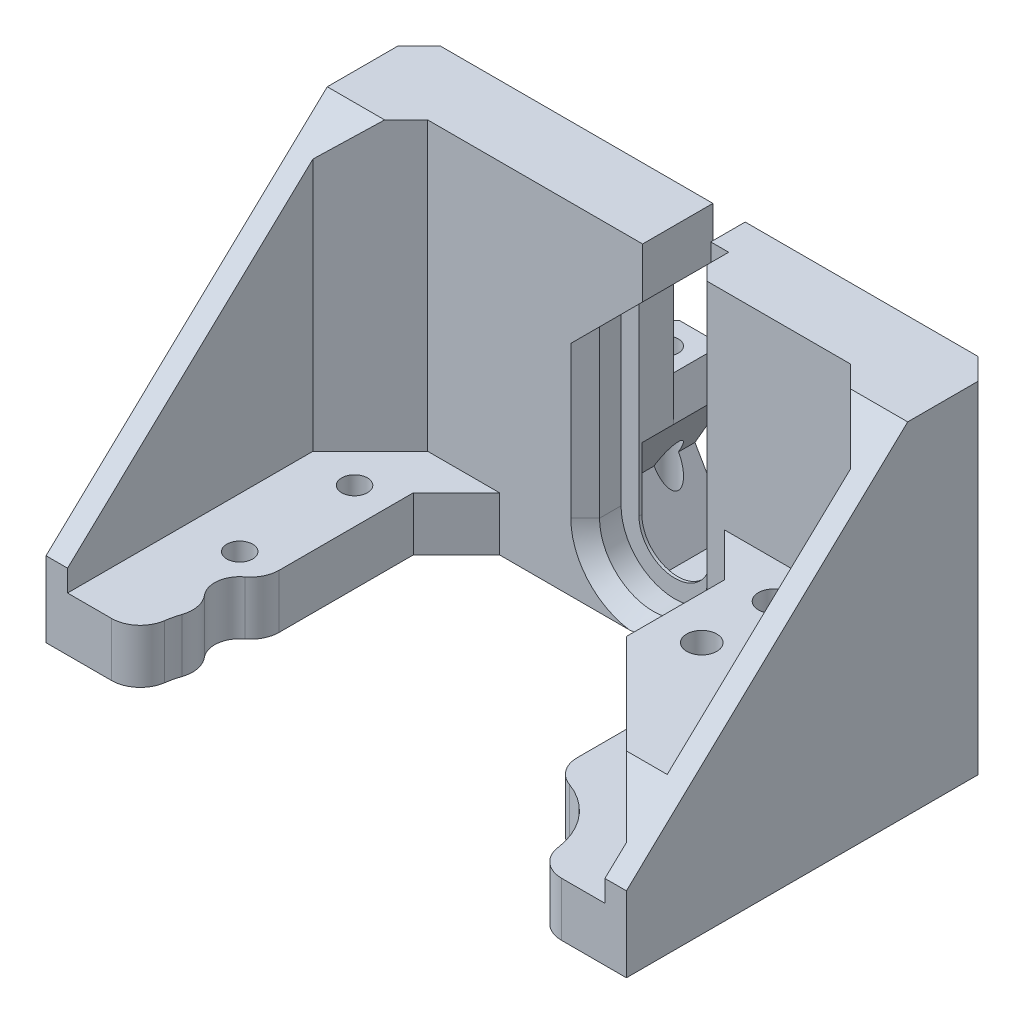
SolidWorks part; units mm, degrees
ref_plane "Front Plane" through (0, 0, 0) normal (0, 0, 1) x (1, 0, 0)
ref_plane "Top Plane" through (0, 0, 0) normal (0, 1, 0) x (1, 0, 0)
ref_plane "Right Plane" through (0, 0, 0) normal (1, 0, 0) x (0, 0, -1)
sketch "Sketch1" plane through (0, 0, 0) normal (0, 1, 0) x (1, 0, 0)
  line L0 (0, 0) -> (0, -16) construction
  line L1 (54.39, 4) -> (54.39, -6) construction
  line L2 (48.39, 9.2) -> (48.39, -33)
  line L3 (48.39, -33) -> (67.89, -33)
  line L4 (67.89, -33) -> (67.89, 19)
  line L5 (67.89, 19) -> (-7, 19)
  line L6 (-7, 19) -> (-7, -33)
  line L7 (-7, -33) -> (5, -33)
  line L8 (5, -33) -> (5, 9.2)
  line L9 (5, 9.2) -> (48.39, 9.2)
  circle A0 centre (0, 0) radius 1
  circle A1 centre (0, -16) radius 1
  circle A2 centre (54.39, 4) radius 1
  circle A3 centre (54.39, -6) radius 1
  dimension "D1" = 16
  dimension "D2" = 10
  dimension "D3" = 10
  dimension "D5" = 17
  dimension "D7" = 2
  dimension "D10" = 9.2
  dimension "D4" = 52
  dimension "D6" = 5
  dimension "D8" = 6
  dimension "D9" = 54.39
  dimension "D11" = 12
  dimension "D12" = 19.5
extrude "Boss-Extrude1" add sketch "Sketch1" along normal blind 7.5
hole_wizard "CSK for M3 Hex Socket Countersunk Head Screw1" positions "Sketch2" profile "Sketch3" countersink size "M3" standard "DIN" end condition through all
sketch "Sketch2" plane through (0, 0, 0) normal (0, -1, 0) x (-1, 0, 0)
  point P0 (0, 0)
  point P3 (0, -16)
  point P6 (-54.39, 4)
  point P9 (-54.39, -6)
sketch "Sketch3" plane through (0, 0, 0) normal (1, 0, 0) x (0, 0, -1)
  line L0 (0, 0) -> (0, 7.5)
  line L1 (0, 7.5) -> (1.8, 7.5)
  line L2 (1.8, 7.5) -> (1.8, 1.67)
  line L3 (1.8, 1.67) -> (3.47, 0)
  line L5 (3.47, 0) -> (0, 0)
  line L6 (-1.8, 1.67) -> (-3.47, 0) construction
  line L11 (0, -6.35) -> (0, 107.95) construction
  dimension "Thru Hole Dia." = 3.6
  dimension "Thru Hole Depth" = 7.5
  dimension "Near C'Sink Dia." = 6.94
  dimension "Near C'Sink Angle" = 90
sketch "Sketch4" plane through (0, 7.5, 0) normal (0, 1, 0) x (1, 0, 0)
  line L0 (67.89, -33) -> (67.89, 19) construction
  line L1 (-7, 19) -> (67.89, 19)
  line L2 (-7, 19) -> (-7, 9.2)
  line L3 (-7, 9.2) -> (67.89, 9.2)
  line L4 (67.89, 19) -> (67.89, 9.2)
  line L5 (5, 9.2) -> (48.39, 9.2) construction
extrude "Boss-Extrude2" add sketch "Sketch4" along normal blind 40
sketch "Sketch5" plane through (-7, 0, 0) normal (-1, 0, 0) x (0, 0, 1)
  line L0 (-19, 47.5) -> (-6.2, 47.5)
  line L1 (-6.2, 47.5) -> (33, 10.5)
  line L2 (33, 10.5) -> (33, 0)
  line L3 (33, 0) -> (-19, 0)
  line L4 (-19, 0) -> (-19, 47.5)
  line L5 (-9.2, 47.5) -> (-9.2, 7.5) construction
  line L6 (-9.2, 7.5) -> (33, 7.5) construction
  dimension "D1" = 3
  dimension "D2" = 3
extrude "Boss-Extrude3" add sketch "Sketch5" along normal blind 3
extrude "Boss-Extrude4" add sketch "Sketch5<2>" against normal blind 3 from surface starting at face at (67.89, 18.3333, 1.6)
sketch "Sketch5<2>" plane through (-7, 0, 0) normal (-1, 0, 0) x (0, 0, 1) same geometry as "Sketch5"
sketch "Sketch6" plane through (0, 0, 0) normal (0, -1, 0) x (1, 0, 0)
  line L0 (3, 31) -> (3, 33)
  line L1 (-10, 33) -> (5, 33) construction
  line L2 (3, 33) -> (5, 33)
  line L3 (5, 33) -> (5, 24.8356)
  line L4 (5, 33) -> (5, -9.2) construction
  circle A0 centre (13.5, 31) radius 9.5 construction
  circle A1 centre (13.5, 31) radius 9.5 construction
  arc A2 (3, 31) -> (5, 24.8356) centre (13.5, 31) ccw
  circle A3 centre (13.5, 31) radius 10.5 construction
  circle A4 centre (5.5, 21.5) radius 1.5 construction
  circle A5 centre (5.5, 21.5) radius 1.5 construction
  circle A6 centre (5.5, 21.5) radius 3.5
  circle A7 centre (47.5, 31) radius 9.5 construction
  circle A8 centre (47.5, 31) radius 9.5 construction
  circle A9 centre (47.5, 31) radius 10.5
  line M7 (5, -9.2) -> (5, 33)
  line M8 (5, 33) -> (-10, 33)
  dimension "D2" = 2
  dimension "D1" = 1
  dimension "D3" = 1
extrude "Cut-Extrude1" cut sketch "Sketch6" against normal through all contours A6 L3 L0 A2 M8 | A6 A2 M7 | A2 A6 M7 | A9 region at (4.1304, 0, 29.7376) region at (4.9724, 0, 24.917) region at (3.7405, 0, 21.4988)
fillet "Fillet1" radius 4 5 edges at (3, 3.75, 33) (4.9174, 3.75, 24.9512) (5, 3.75, 18.0359) (57.8078, 3.75, 33) (48.39, 3.75, 20.5378)
sketch "Sketch7" plane through (0, 7.5, 0) normal (0, 1, 0) x (1, 0, 0)
  line L0 (67.89, -33) -> (67.89, 9.2) construction
  line L1 (48.39, 9.2) -> (67.89, 9.2)
  line L2 (48.39, 9.2) -> (48.39, -10)
  line L3 (48.39, -10) -> (67.89, -10)
  line L4 (67.89, 9.2) -> (67.89, -10)
  circle A0 centre (54.39, -6) radius 4 construction
  dimension "D1" = 8
extrude "Boss-Extrude5" add sketch "Sketch7" along normal blind 6 from offset 5.2
hole_wizard "Ø4.2 (4.2) Diameter Hole1" positions "Sketch8" profile "Sketch10" hole size "Ø4.2" standard "DIN" end condition through all
sketch "Sketch8" plane through (0, 12.7, 0) normal (0, -1, 0) x (-1, 0, 0)
  point P0 (-54.39, -6)
  point P3 (-54.39, 4)
sketch "Sketch10" plane through (54.39, 12.7, 6) normal (1, 0, 0) x (0, 0, -1)
  line L0 (0, 0) -> (0, 34.8)
  line L1 (0, 34.8) -> (2.1, 34.8)
  line L2 (2.1, 34.8) -> (2.1, 0)
  line L5 (2.1, 0) -> (0, 0)
  line L11 (0, -6.35) -> (0, 107.95) construction
  dimension "Thru Hole Dia." = 4.2
  dimension "Thru Hole Depth" = 34.8
chamfer "Chamfer1" distance 20 angle 45 1 edges at (67.89, 15.7, 10)
chamfer "Chamfer2" distance 8 angle 45 2 edges at (-7, 27.5, -9.2) (67.89, 33.1, -9.2)
chamfer "Chamfer3" distance 3 angle 45 2 edges at (70.89, 23.75, -19) (-10, 23.75, -19)
chamfer "Chamfer4" distance 6 angle 45 3 edges at (48.39, 15.7, -9.2) (48.39, 3.75, -9.2) (5, 3.75, -9.2)
sketch "Sketch11" plane through (0, 0, -19) normal (0, 0, -1) x (-1, 0, 0)
  line L0 (-70.89, 0) -> (-70.89, 47.5) construction
  line L1 (10, 47.5) -> (10, 0) construction
  line L2 (-70.89, 0) -> (-70.89, 47.5) construction
  line L3 (10, 47.5) -> (10, 0) construction
  line L4 (-70.89, 9.4) -> (-30.445, 9.4) construction
  line L5 (-30.445, 9.4) -> (10, 9.4) construction
  line L6 (-67.89, 0) -> (7, 0) construction
  line L7 (-35.445, 9.4) -> (-35.445, 47.5)
  line L8 (-67.89, 47.5) -> (7, 47.5) construction
  line L9 (-35.445, 47.5) -> (-25.445, 47.5)
  line L10 (-25.445, 47.5) -> (-25.445, 9.4)
  arc A0 (-35.445, 9.4) -> (-25.445, 9.4) centre (-30.445, 9.4) ccw
  dimension "D1" = 9.4
  dimension "D2" = 10
extrude "Cut-Extrude2" cut sketch "Sketch11" against normal through all
sketch "Sketch13" plane through (0, 0, -19) normal (0, 0, -1) x (-1, 0, 0)
  line L0 (-25.445, 9.4) -> (-25.445, 47.5) construction
  line L1 (-35.445, 47.5) -> (-35.445, 9.4) construction
  line L2 (-25.445, 9.4) -> (-25.445, 17.3599)
  line L3 (-35.445, 17.3599) -> (-35.445, 9.4)
  arc A0 (-35.445, 17.3599) -> (-25.445, 17.3599) centre (-30.445, 9.4) ccw
  arc A1 (-35.445, 9.4) -> (-25.445, 9.4) centre (-30.445, 9.4) ccw construction
  arc A2 (-35.445, 9.4) -> (-25.445, 9.4) centre (-30.445, 9.4) ccw
extrude "Boss-Extrude7" [suppressed] add sketch "Sketch13" along normal blind 10
sketch "Sketch14" plane through (0, 0, -9.2) normal (0, 0, 1) x (1, 0, 0)
  line L0 (22.945, 9.4) -> (22.945, 47.5)
  line L1 (1, 47.5) -> (25.445, 47.5) construction
  line L2 (22.945, 47.5) -> (37.945, 47.5)
  line L3 (35.445, 47.5) -> (59.89, 47.5) construction
  line L4 (37.945, 47.5) -> (37.945, 9.4)
  arc A0 (22.945, 9.4) -> (37.945, 9.4) centre (30.445, 9.4) ccw
  dimension "D1" = 15
extrude "Cut-Extrude3" cut sketch "Sketch14" against normal blind 5
sketch "Sketch12" plane through (0, 0, -9.2) normal (0, 0, -1) x (-1, 0, 0)
  line L0 (-22.945, 47.5) -> (-30.945, 47.5)
  line L1 (-30.945, 47.5) -> (-30.945, 40.5)
  line L2 (-30.945, 40.5) -> (-22.945, 32.5)
  line L4 (-22.945, 32.5) -> (-22.945, 47.5)
  line L5 (-35.445, 47.5) -> (-35.445, 9.4) construction
  line L7 (-22.945, 47.5) -> (-22.945, 9.4) construction
  line L8 (-1, 47.5) -> (-22.945, 47.5) construction
  dimension "D1" = 45
  dimension "D2" = 4.5
  dimension "D3" = 15
extrude "Boss-Extrude6" add sketch "Sketch12" along normal up to surface (9.8 mm away) up to face at (30.445, 25.475, -19)
chamfer "Chamfer5" [suppressed] distance 3 angle 45
sketch "Sketch15" plane through (0, 0, -19) normal (0, 0, -1) x (-1, 0, 0)
  line L0 (-21.121, -2.35) -> (-39.769, -2.35)
  line L1 (-35.445, 18.0603) -> (-40.445, 9.4)
  line L2 (-40.445, 9.4) -> (-35.445, 0.7397)
  line L3 (-35.445, 0.7397) -> (-25.445, 0.7397)
  line L4 (-25.445, 0.7397) -> (-20.445, 9.4)
  line L5 (-20.445, 9.4) -> (-25.445, 18.0603)
  line L6 (-25.445, 18.0603) -> (-35.445, 18.0603)
  line L7 (-36.695, 23.0359) -> (-35.445, 18.0603)
  line L8 (-25.445, 18.0603) -> (-24.195, 23.0359)
  circle A0 centre (-30.445, 9.4) radius 10 construction
  circle A1 centre (-30.445, 9.4) radius 8.6603 construction
  arc A2 (-21.121, -2.35) -> (-39.769, -2.35) centre (-30.445, 9.4) ccw
  line M13 (-25.445, 35) -> (-25.445, 9.4)
  line M15 (-35.445, 9.4) -> (-35.445, 47.5)
  line M18 (-67.89, 0) -> (7, 0)
  dimension "D1" = 20
  dimension "D2" = 30
extrude "Boss-Extrude8" add sketch "Sketch15" along normal blind 8 contours A2 L5 L4 L3 L2 L1 M15 M18 M13 region at (30.445, 0.3782, -19)
sketch "Sketch16" plane through (0, 0, -19) normal (0, 0, -1) x (-1, 0, 0)
  line L7 (-25.445, 0.7397) -> (-20.445, 9.4)
  line L8 (-20.445, 9.4) -> (-25.445, 18.0603)
  line L9 (-25.445, 18.0603) -> (-25.445, 9.4)
  line L10 (-35.445, 9.4) -> (-35.445, 18.0603)
  line L11 (-35.445, 18.0603) -> (-40.445, 9.4)
  line L12 (-40.445, 9.4) -> (-35.445, 0.7397)
  line L13 (-35.445, 0.7397) -> (-25.445, 0.7397)
  line L14 (-25.445, 0.7397) -> (-20.445, 9.4)
  line L15 (-20.445, 9.4) -> (-25.445, 18.0603)
  line L16 (-25.445, 18.0603) -> (-25.445, 9.4)
  line L17 (-35.445, 9.4) -> (-35.445, 18.0603)
  line L18 (-35.445, 18.0603) -> (-40.445, 9.4)
  line L19 (-40.445, 9.4) -> (-35.445, 0.7397)
  line L20 (-35.445, 0.7397) -> (-25.445, 0.7397)
  arc A1 (-35.445, 9.4) -> (-25.445, 9.4) centre (-30.445, 9.4) ccw
  arc A2 (-35.445, 9.4) -> (-25.445, 9.4) centre (-30.445, 9.4) ccw
  dimension "D1" = 0
extrude "Cut-Extrude4" cut sketch "Sketch16" against normal blind 4.4
chamfer "Chamfer6" [suppressed] distance 2 angle 45
sketch "Sketch18" plane through (0, 0, -19) normal (0, 0, -1) x (-1, 0, 0)
  line L0 (-67.89, 0) -> (-42.1343, 0) construction
  line L1 (-45.445, 0) -> (-42.1343, 0)
  line L2 (-45.445, 0) -> (-45.445, 23.0359)
  line L3 (-45.445, 23.0359) -> (-36.695, 23.0359)
  line L4 (-15.445, 0) -> (-15.445, 23.0359)
  line L5 (-24.195, 23.0359) -> (-15.445, 23.0359)
  line L6 (-18.7557, 0) -> (-15.445, 0)
  arc A0 (-18.7557, 0) -> (-24.195, 23.0359) centre (-30.445, 9.4) ccw construction
  arc A1 (-36.695, 23.0359) -> (-42.1343, 0) centre (-30.445, 9.4) ccw construction
  arc A2 (-18.7557, 0) -> (-24.195, 23.0359) centre (-30.445, 9.4) ccw construction
  arc A3 (-18.7557, 0) -> (-24.195, 23.0359) centre (-30.445, 9.4) ccw
  arc A4 (-36.695, 23.0359) -> (-42.1343, 0) centre (-30.445, 9.4) ccw
  arc M5 (-24.195, 23.0359) -> (-18.7557, 0) centre (-30.445, 9.4) cw
  line M6 (-18.7557, 0) -> (7, 0)
extrude "Boss-Extrude9" add sketch "Sketch18" along normal up to surface (8 mm away) contours A4 L2 L1 | L4 M6 M5 | L5 L4 M5 | A4 L3 L2 region at (44.4739, 2.295, -19) region at (43.036, 19.8558, -19) region at (16.4161, 2.295, -19) region at (17.854, 19.8558, -19) up to face at (30.445, 10.513, -27)
sketch "Sketch17" plane through (0, 0, 0) normal (0, -1, 0) x (1, 0, 0)
  line L0 (20.445, -27) -> (20.445, -14.6) construction
  line L1 (20.445, -27) -> (20.445, -14.6) construction
  line L2 (30.445, -27) -> (30.445, -19) construction
  line L3 (45.445, -27) -> (15.445, -27) construction
  line L4 (67.89, -19) -> (45.445, -19) construction
  line L5 (30.445, -23) -> (20.445, -23) construction
  circle A0 centre (20.445, -23) radius 1
  circle A1 centre (40.445, -23) radius 1
  point P11 (30.445, -27)
  dimension "D1" = 2
extrude "Cut-Extrude5" cut sketch "Sketch17" against normal through all
hole_wizard "M3 Clearance Hole1" positions "Sketch19" profile "Sketch20" hole size "M3" standard "DIN" end condition through all
sketch "Sketch19" plane through (0, 0, 0) normal (0, -1, 0) x (-1, 0, 0)
  point P0 (-20.445, 23)
  point P3 (-40.445, 23)
sketch "Sketch20" plane through (20.445, 0, -23) normal (1, 0, 0) x (0, 0, -1)
  line L0 (0, 0) -> (0, 47.5)
  line L1 (0, 47.5) -> (1.7, 47.5)
  line L2 (1.7, 47.5) -> (1.7, 0)
  line L5 (1.7, 0) -> (0, 0)
  line L11 (0, -6.35) -> (0, 107.95) construction
  dimension "Thru Hole Dia." = 3.4
  dimension "Thru Hole Depth" = 47.5
chamfer "Chamfer9" distance 8 angle 45 2 edges at (45.445, 11.5179, -19) (15.445, 11.5179, -19)
chamfer "Chamfer7" distance 2 angle 45 4 edges at (11.445, 0, -23) (11.445, 23.0359, -23) (49.445, 23.0359, -23) (49.445, 0, -23)
chamfer "Chamfer8" distance 2 angle 45 3 edges at (22.945, 20.95, -9.2) (30.445, 1.9, -9.2) (37.945, 28.45, -9.2)
